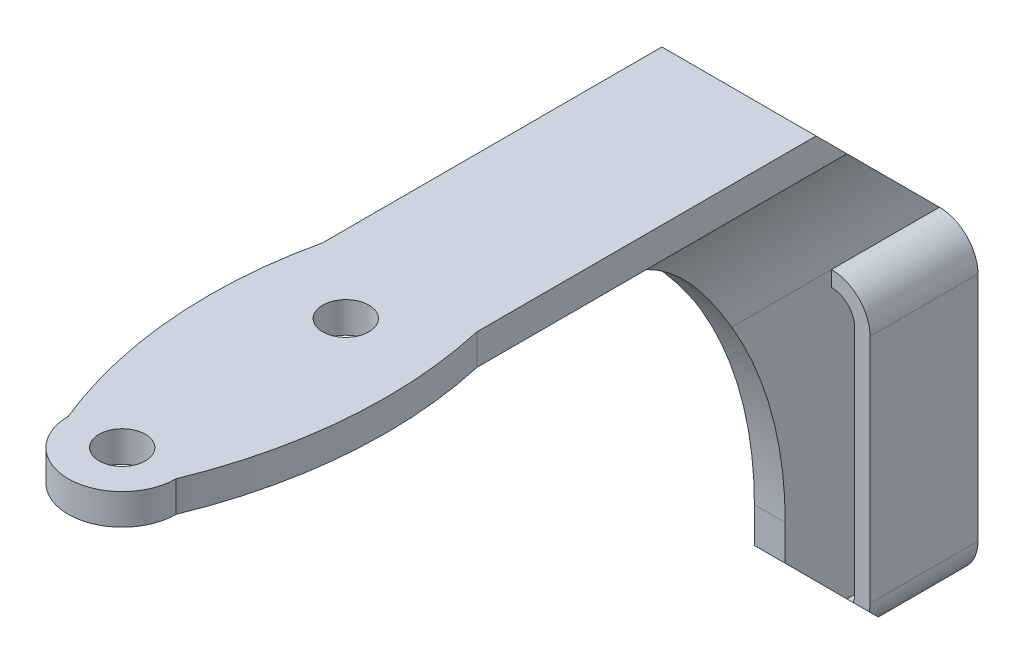
SolidWorks part; units mm, degrees
ref_plane "Front Plane" through (0, 0, 0) normal (0, 0, 1) x (1, 0, 0)
ref_plane "Top Plane" through (0, 0, 0) normal (0, 1, 0) x (1, 0, 0)
ref_plane "Right Plane" through (0, 0, 0) normal (1, 0, 0) x (0, 0, -1)
sketch "Sketch1" plane through (0, 0, 0) normal (0, 1, 0) x (1, 0, 0)
  line L0 (-5, 18) -> (5, 18) construction
  line L1 (-5, 18) -> (-5, 40)
  line L2 (5, 18) -> (5, 40)
  line L3 (-5, 40) -> (5, 40)
  circle A0 centre (0, 0) radius 3.5
  arc A1 (-3.5, 0) -> (-5, 18) centre (24.2595, 11.3758) cw
  arc A2 (3.5, 0) -> (5, 18) centre (-24.2595, 11.3758) ccw
  circle A3 centre (0, 0) radius 1.5
  circle A4 centre (0, 14.5) radius 1.5
  point P9 (0, 18)
  dimension "D1" = 7
  dimension "D2" = 10
  dimension "D4" = 30
  dimension "D6" = 3
  dimension "D7" = 3
  dimension "D3" = 18
  dimension "D5" = 40
  dimension "D8" = 14.5
extrude "Boss-Extrude1" add sketch "Sketch1" along normal blind 2 contours L1 L0 L2 L3 | L0 A1 A0 A2 A4 | A0 A3 region at (0, 0, -29) region at (0, 0, -10.1546) region at (0, 0, -3.401)
sketch "Sketch2" plane through (-5, 0, 0) normal (-1, 0, 0) x (0, 0, 1)
  line L0 (-40, 2) -> (-50, -8)
  line L1 (-18, 2) -> (-40, 2) construction
  line L2 (-40, 2) -> (-29, 0)
  line L3 (-18, 0) -> (-40, 0) construction
  line L4 (-50, -8) -> (-50, -28)
  line L5 (-50, -28) -> (-40, -28)
  line L6 (-40, -28) -> (-40, -20.7123)
  arc A0 (-29, 0) -> (-40, -20.7123) centre (-15, -20.7123) ccw
  dimension "D2" = 20
  dimension "D5" = 25
  dimension "D1" = 45
  dimension "D3" = 10
  dimension "D4" = 10
extrude "Boss-Extrude2" add sketch "Sketch2" against normal up to surface (10 mm away) up to face at (5, 1, -29)
sketch "Sketch3" plane through (0, 0, -50) normal (0, 0, -1) x (-1, 0, 0)
  line L0 (-5, -28) -> (5, -28) construction
  line L1 (-5, -8) -> (5, -8) construction
  line L6 (-3, -8) -> (-3, -28)
  line L7 (-3, -28) -> (-5, -28)
  line L8 (-5, -28) -> (-5, 0)
  line L9 (-1, -8) -> (-1, -28)
  line L10 (-1, -28) -> (5, -28)
  line L11 (5, -28) -> (5, 0)
  arc A2 (-5, 0) -> (-3, -8) centre (-20, -8) cw
  arc A3 (5, 0) -> (-1, -8) centre (7.3333, -8) ccw
  dimension "D1" = 2
  dimension "D2" = 2
extrude "Cut-Extrude1" cut sketch "Sketch3" against normal up to next
sketch "Sketch4" plane through (0, 0, -50) normal (0, 0, -1) x (-1, 0, 0)
  line L0 (-5.5, -10.5) -> (-5.5, -25.5)
  line L1 (-4.5, -10.5) -> (-4.5, -25.5)
  line L2 (-3, -28) -> (-3, -8) construction
  arc A0 (-3, -8) -> (-5.5, -10.5) centre (-3, -10.5) ccw
  arc A1 (-3, -28) -> (-5.5, -25.5) centre (-3, -25.5) cw
  arc A2 (-3, -9) -> (-4.5, -10.5) centre (-3, -10.5) ccw
  arc A3 (-3, -27) -> (-4.5, -25.5) centre (-3, -25.5) cw
  line M1 (-3, -8) -> (-3, -28)
  dimension "D1" = 1
  dimension "D2" = 1.5
extrude "Boss-Extrude3" add sketch "Sketch4" against normal blind 7 contours A3 L1 A2 A0 L0 A1 M1 region at (4.7933, -18, -50)
chamfer "Chamfer1" distance 5 angle 45 1 edges at (2, -28, -40)
